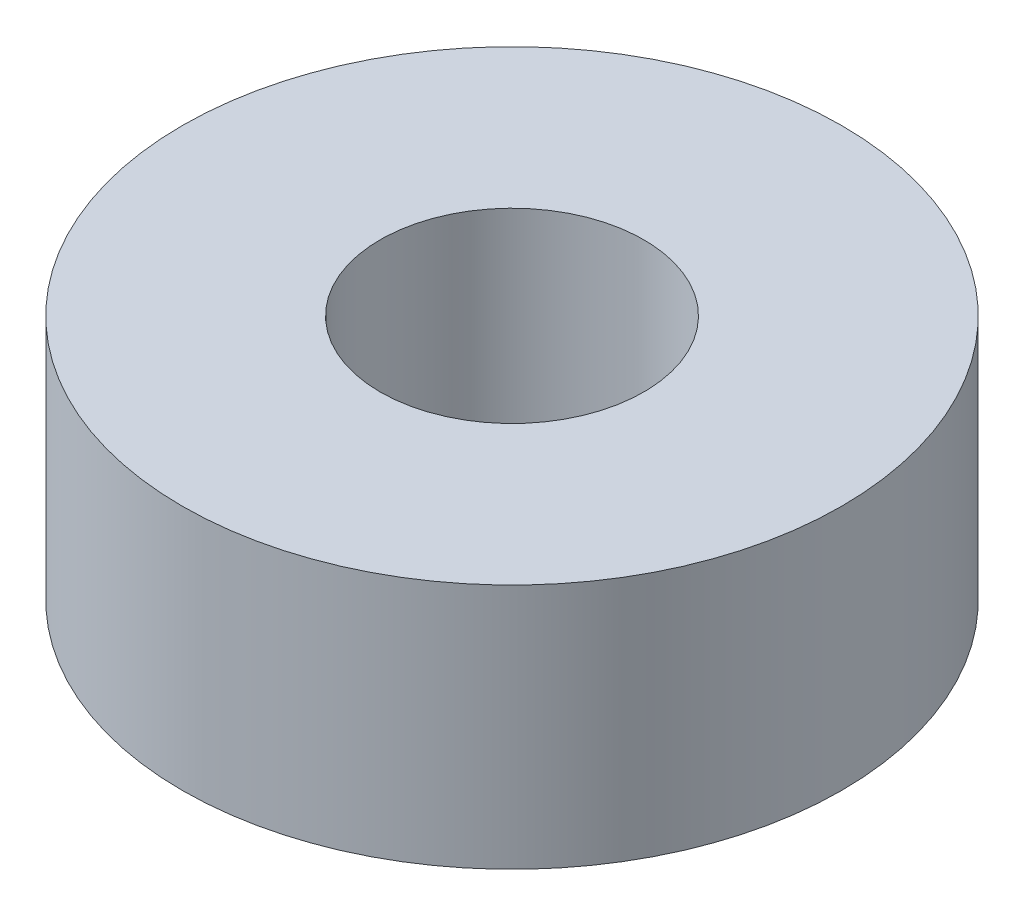
SolidWorks part; units mm, degrees
ref_plane "Front Plane" through (0, 0, 0) normal (0, 0, 1) x (1, 0, 0)
ref_plane "Top Plane" through (0, 0, 0) normal (0, 1, 0) x (1, 0, 0)
ref_plane "Right Plane" through (0, 0, 0) normal (1, 0, 0) x (0, 0, -1)
sketch "Sketch1" plane through (0, 0, 0) normal (0, 1, 0) x (1, 0, 0)
  circle A0 centre (0, 0) radius 37.5
  dimension "FLANGE_OD" = 75
extrude "Boss-Extrude1" add sketch "Sketch1" along normal blind 28
sketch "Sketch2" plane through (0, 0, 0) normal (0, 1, 0) x (1, 0, 0)
  circle A0 centre (0, 0) radius 15
  dimension "BORE_D" = 30
extrude "Cut-Extrude1" cut sketch "Sketch2" along normal through all
sketch "Sketch3" plane through (0, 28, 0) normal (0, 1, 0) x (1, 0, 0)
  circle A0 centre (0, 0) radius 11.0135 construction
  circle A1 centre (-11.0135, 0) radius 3.6142
  dimension "BOLT_D" = 7.2285
  dimension "BOLT_PCD" = 22.0269
extrude "Cut-Extrude2" cut sketch "Sketch3" against normal blind 27.9219 rebuild error yes
pattern_circular "CirPattern1" count 3 over 360 rebuild error yes
